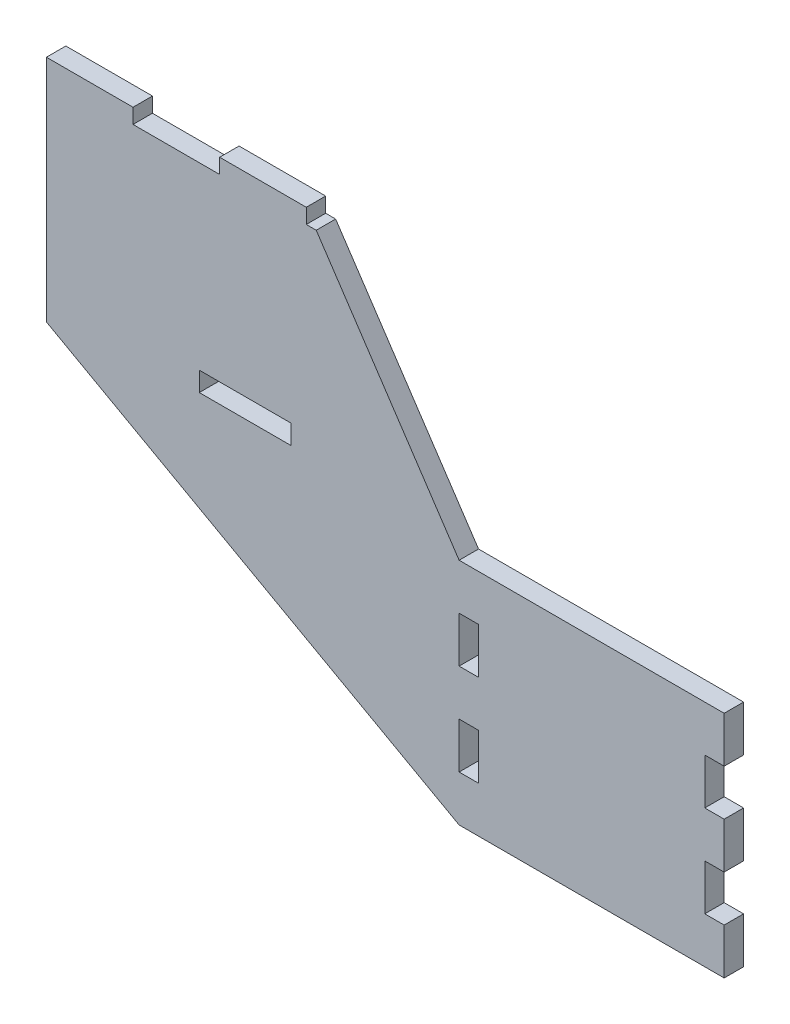
SolidWorks part; units mm, degrees
ref_plane "Front Plane" through (0, 0, 0) normal (0, 0, 1) x (1, 0, 0)
ref_plane "Top Plane" through (0, 0, 0) normal (0, 1, 0) x (1, 0, 0)
ref_plane "Right Plane" through (0, 0, 0) normal (1, 0, 0) x (0, 0, -1)
sketch "Sketch1" plane through (0, 0, 0) normal (0, 0, 1) x (1, 0, 0)
  line L0 (86.7, -75) -> (86.7, 0)
  line L1 (86.7, 0) -> (0, 0)
  line L2 (0, 0) -> (-50, 75)
  line L3 (-50, 75) -> (-135, 75)
  line L4 (-135, 75) -> (-135, 0)
  line L5 (-135, 0) -> (0, -75)
  line L6 (0, -75) -> (86.7, -75)
  point P10 (0, 0)
  point P19 (86.7, 0)
  dimension "D5" = 50
  dimension "D1" = 86.7
  dimension "D2" = 75
  dimension "D3" = 85
  dimension "D4" = 150
extrude "Body" add sketch "Sketch1" along normal blind 6.35
sketch "Sketch2" plane through (0, 0, 6.35) normal (0, 0, 1) x (1, 0, 0)
  line L1 (-85, 5) -> (-55, 5)
  line L2 (-85, 5) -> (-85, 11.35)
  line L3 (-85, 11.35) -> (-55, 11.35)
  line L4 (-55, 5) -> (-55, 11.35)
  line L7 (86.7, 0) -> (0, 0) construction
  line L8 (-135, 75) -> (-135, 0) construction
  dimension "D1" = 6.35
  dimension "D2" = 30
  dimension "D3" = 50
  dimension "D4" = 5
extrude "Cross support" cut sketch "Sketch2" against normal up to next
sketch "Sketch3" plane through (0, 0, 6.35) normal (0, 0, 1) x (1, 0, 0)
  line L0 (86.7, -15) -> (80.35, -15)
  line L1 (86.7, -75) -> (86.7, 0) construction
  line L2 (80.35, -15) -> (80.35, -30)
  line L3 (80.35, -30) -> (86.7, -30)
  line L4 (86.7, -15) -> (86.7, -30)
  line L5 (86.7, -45) -> (80.35, -45)
  line L6 (80.35, -45) -> (80.35, -60)
  line L7 (80.35, -60) -> (86.7, -60)
  line L8 (86.7, -45) -> (86.7, -60)
  line L9 (80.35, 0) -> (80.35, -15) construction
  line L10 (86.7, 0) -> (0, 0) construction
  line L11 (80.35, -30) -> (80.35, -45) construction
  line L12 (80.35, -60) -> (80.35, -75) construction
  line L13 (0, -75) -> (86.7, -75) construction
  line L14 (0, 0) -> (0, -75) construction
  line L15 (0, -45) -> (6.35, -45)
  line L16 (0, -30) -> (0, -15)
  line L17 (0, -15) -> (6.35, -15)
  line L18 (6.35, -30) -> (6.35, -15)
  line L19 (6.35, -30) -> (0, -30)
  line L20 (6.35, -45) -> (6.35, -60)
  line L21 (6.35, -60) -> (0, -60)
  line L22 (0, -60) -> (0, -45)
  line L23 (86.7, 0) -> (0, 0) construction
  line L24 (6.35, -15) -> (6.35, 0) construction
  line L25 (6.35, -30) -> (6.35, -45) construction
  line L26 (6.35, -60) -> (6.35, -75) construction
  dimension "D1" = 6.35
  dimension "D2" = 6.35
extrude "Side supports" cut sketch "Sketch3" against normal up to next
sketch "Sketch4" plane through (0, 0, 6.35) normal (0, 0, 1) x (1, 0, 0)
  line L0 (-106.6667, 75) -> (-106.6667, 70.1161)
  line L2 (-50, 75) -> (-135, 75) construction
  line L4 (-106.6667, 70.1161) -> (-78.3333, 70.1161)
  line L5 (-78.3333, 70.1161) -> (-78.3333, 75)
  line L6 (-78.3333, 75) -> (-106.6667, 75)
  line L7 (-46.7441, 70.1161) -> (-50, 70.1161)
  line L8 (0, 0) -> (-50, 75) construction
  line L9 (-50, 70.1161) -> (-50, 75)
  line L10 (-50, 75) -> (-46.7441, 70.1161)
  line L11 (-135, 70.1161) -> (-106.6667, 70.1161) construction
  line L12 (-135, 75) -> (-135, 0) construction
  line L13 (-78.3333, 70.1161) -> (-50, 70.1161) construction
extrude "Top mounting teeth" cut sketch "Sketch4" against normal up to next
